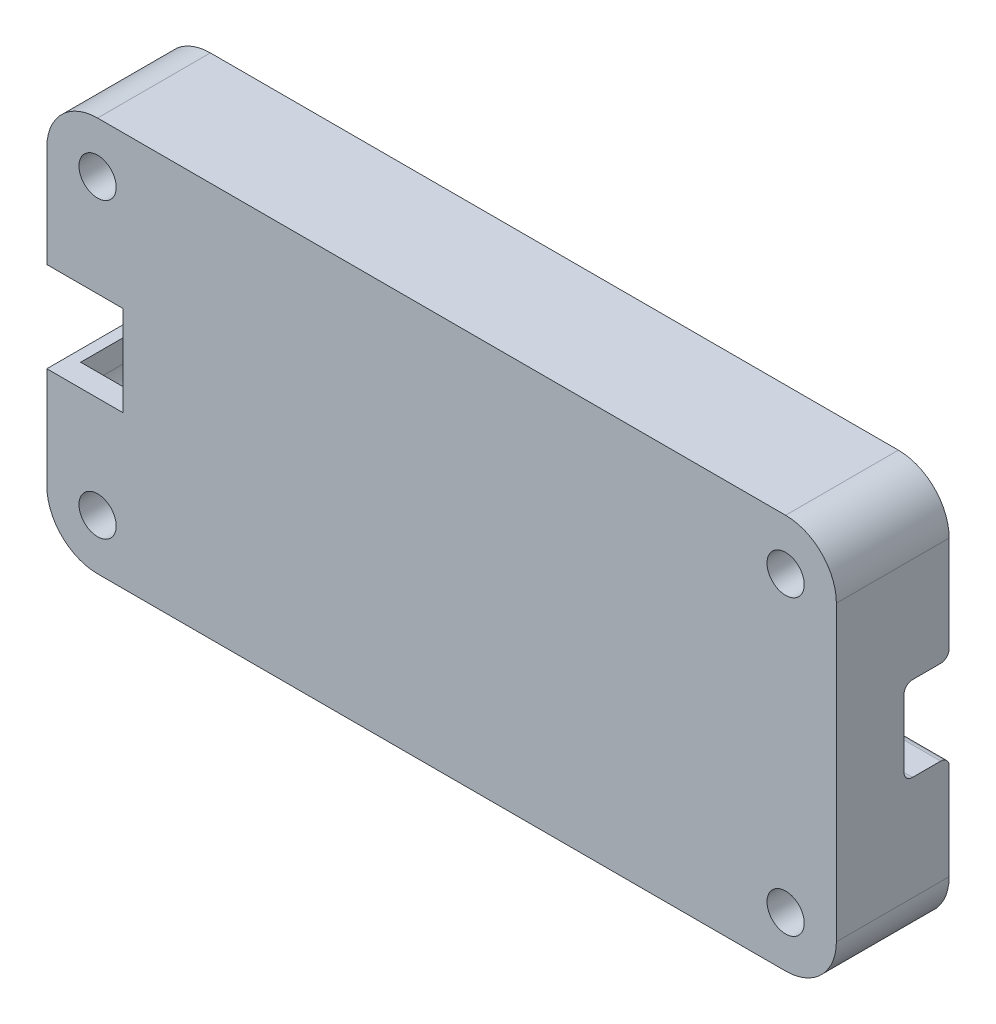
SolidWorks part; units mm, degrees
ref_plane "Front Plane" through (0, 0, 0) normal (0, 0, 1) x (1, 0, 0)
ref_plane "Top Plane" through (0, 0, 0) normal (0, 1, 0) x (1, 0, 0)
ref_plane "Right Plane" through (0, 0, 0) normal (1, 0, 0) x (0, 0, -1)
sketch "Sketch1" plane through (0, 0, 0) normal (0, 0, 1) x (1, 0, 0)
  line L1 (-35, -17.5) -> (35, -17.5)
  line L2 (-35, -17.5) -> (-35, 17.5)
  line L3 (-35, 17.5) -> (35, 17.5)
  line L4 (35, -17.5) -> (35, 17.5)
  line L5 (-35, -17.5) -> (35, 17.5) construction
  line L6 (-35, 17.5) -> (35, -17.5) construction
  point P0 (0, 0)
  dimension "D1" = 70
  dimension "D2" = 35
extrude "Boss-Extrude1" add sketch "Sketch1" along normal blind 10
fillet "Fillet1" radius 4.5 4 edges at (-35, -17.5, 5) (35, -17.5, 5) (35, 17.5, 5) (-35, 17.5, 5)
sketch "Sketch2" plane through (0, 0, 10) normal (0, 0, 1) x (1, 0, 0)
  circle A0 centre (-30.5, 13) radius 1.65
  circle A1 centre (30.5, 13) radius 1.65
  circle A2 centre (30.5, -13) radius 1.65
  circle A3 centre (-30.5, -13) radius 1.65
  dimension "D1" = 3.3
extrude "Cut-Extrude1" cut sketch "Sketch2" against normal blind 10
sketch "Sketch3" plane through (0, 0, 0) normal (0, 0, -1) x (-1, 0, 0)
  line L1 (-25.5, -15) -> (25.5, -15)
  line L2 (-25.5, -15) -> (-25.5, 15)
  line L3 (-25.5, 15) -> (25.5, 15)
  line L4 (25.5, -15) -> (25.5, 15)
  line L5 (-25.5, -15) -> (25.5, 15) construction
  line L6 (-25.5, 15) -> (25.5, -15) construction
  point P0 (0, 0)
  dimension "D1" = 30
  dimension "D2" = 51
extrude "Cut-Extrude2" cut sketch "Sketch3" against normal blind 8
sketch "Sketch4" plane through (0, 0, 0) normal (0, 0, -1) x (-1, 0, 0)
  line L1 (28.25, 4) -> (35, 4)
  line L2 (28.25, 4) -> (28.25, -4)
  line L3 (28.25, -4) -> (35, -4)
  line L4 (35, 4) -> (35, -4)
  line L5 (35, 13) -> (35, -13) construction
  line L6 (30.5, -17.5) -> (-30.5, -17.5) construction
  line L7 (-30.5, 17.5) -> (30.5, 17.5) construction
  dimension "D1" = 13.5
  dimension "D2" = 13.5
  dimension "D3" = 6.75
extrude "Cut-Extrude3" cut sketch "Sketch4" against normal blind 11
sketch "Sketch5" plane through (0, 0, 0) normal (0, 0, -1) x (-1, 0, 0)
  line L1 (34, 8) -> (25.5, 8)
  line L2 (34, 8) -> (34, -8)
  line L3 (34, -8) -> (25.5, -8)
  line L4 (25.5, 8) -> (25.5, -8)
  line L5 (25.5, -15) -> (25.5, 15) construction
  line L6 (-30.5, 17.5) -> (30.5, 17.5) construction
  line L7 (30.5, -17.5) -> (-30.5, -17.5) construction
  dimension "D1" = 9.5
  dimension "D2" = 9.5
  dimension "D3" = 8.5
extrude "Cut-Extrude5" cut sketch "Sketch5" against normal blind 8
sketch "Sketch6" plane through (0, 0, 0) normal (0, 0, -1) x (-1, 0, 0)
  line L0 (-35, -13) -> (-35, 13) construction
  line L1 (-35, 3.75) -> (-25.5, 3.75)
  line L2 (-35, 3.75) -> (-35, -3.75)
  line L3 (-35, -3.75) -> (-25.5, -3.75)
  line L4 (-25.5, 3.75) -> (-25.5, -3.75)
  line L5 (-25.5, 15) -> (-25.5, -15) construction
  line L6 (-30.5, 17.5) -> (30.5, 17.5) construction
  line L7 (30.5, -17.5) -> (-30.5, -17.5) construction
  dimension "D1" = 13.75
  dimension "D2" = 13.75
extrude "Cut-Extrude6" cut sketch "Sketch6" against normal blind 4
fillet "Fillet2" radius 0.75 4 edges at (30.25, -3.75, 0) (30.25, -3.75, 4) (30.25, 3.75, 0) (30.25, 3.75, 4)
fillet "Fillet3" radius 5 2 edges at (25.5, -15, 4) (25.5, 15, 4)
fillet "Fillet4" radius 7 2 edges at (-25.5, -8, 4) (-25.5, 8, 4)
fillet "Fillet5" radius 5 2 edges at (-25.5, -15, 4) (-25.5, 15, 4)
fillet "Fillet6" radius 2 2 edges at (-34, -8, 4) (-34, 8, 4)
